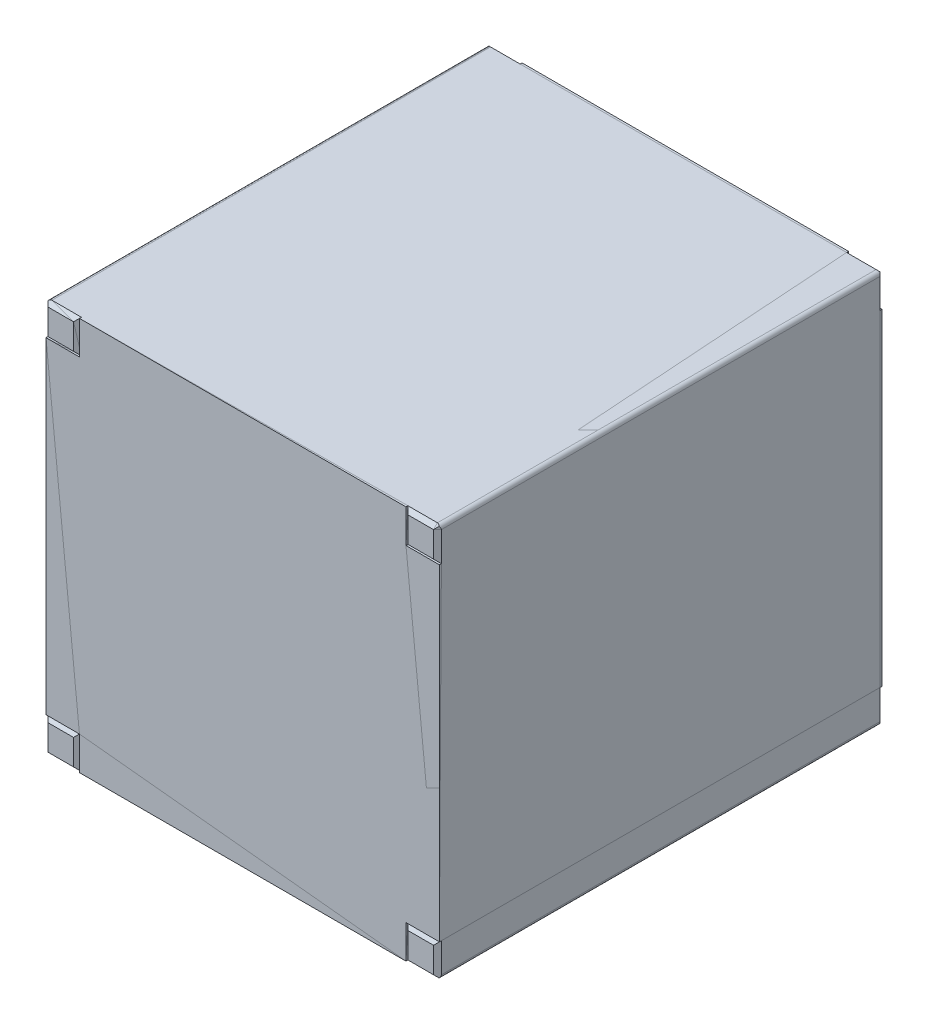
SolidWorks part; units mm, degrees
ref_plane "Front Plane" through (0, 0, 0) normal (0, 0, 1) x (1, 0, 0)
ref_plane "Top Plane" through (0, 0, 0) normal (0, 1, 0) x (1, 0, 0)
ref_plane "Right Plane" through (0, 0, 0) normal (1, 0, 0) x (0, 0, -1)
sketch "Sketch1" plane through (0, 0, 0) normal (0, 0, 1) x (1, 0, 0)
  line L1 (-50, -50) -> (50, -50) construction
  line L2 (-50, -50) -> (-50, 50) construction
  line L3 (-50, 50) -> (50, 50) construction
  line L4 (50, -50) -> (50, 50) construction
  line L5 (-50, -50) -> (50, 50) construction
  line L6 (-50, 50) -> (50, -50) construction
  line L23 (-50, 50) -> (-41.5, 50)
  line L24 (-50, 50) -> (-50, 41.5)
  line L25 (-50, 41.5) -> (-41.5, 41.5)
  line L26 (-41.5, 50) -> (-41.5, 41.5)
  line L27 (50, 50) -> (41.5, 50)
  line L28 (50, 50) -> (50, 41.5)
  line L29 (50, 41.5) -> (41.5, 41.5)
  line L30 (41.5, 50) -> (41.5, 41.5)
  line L31 (50, -50) -> (41.5, -50)
  line L32 (50, -50) -> (50, -41.5)
  line L33 (50, -41.5) -> (41.5, -41.5)
  line L34 (41.5, -50) -> (41.5, -41.5)
  line L35 (-50, -50) -> (-41.5, -50)
  line L36 (-50, -50) -> (-50, -41.5)
  line L37 (-50, -41.5) -> (-41.5, -41.5)
  line L38 (-41.5, -50) -> (-41.5, -41.5)
  point P0 (0, 0)
  dimension "D1" = 100
  dimension "D2" = 100
  dimension "D3" = 8.5
extrude "Boss-Extrude1" add sketch "Sketch1" along normal blind 56.75 and the other way blind 56.75
sketch "Sketch2" plane through (0, 0, 0) normal (0, 0, 1) x (1, 0, 0)
  line L1 (-50, -50) -> (50, -50)
  line L2 (-50, -50) -> (-50, 50)
  line L3 (-50, 50) -> (50, 50)
  line L4 (50, -50) -> (50, 50)
  line L5 (-50, -50) -> (50, 50) construction
  line L6 (-50, 50) -> (50, -50) construction
  point P0 (0, 0)
extrude "Boss-Extrude2" add sketch "Sketch2" along normal blind 50.25 and the other way blind 50.25
chamfer "Chamfer2" distance 1 angle 45 32 edges at (-45.75, -41.5, 56.75) (-41.5, -45.75, 56.75) (-45.75, -50, 56.75) (-50, -45.75, 56.75) (41.5, -45.75, 56.75) (45.75, -41.5, 56.75) (50, -45.75, 56.75) (45.75, -50, 56.75) (45.75, 41.5, 56.75) (41.5, 45.75, 56.75) (45.75, 50, 56.75) (50, 45.75, 56.75) (-41.5, 45.75, 56.75) (-45.75, 41.5, 56.75) (-50, 45.75, 56.75) (-45.75, 50, 56.75) (41.5, 45.75, -56.75) (45.75, 41.5, -56.75) (50, 45.75, -56.75) (45.75, 50, -56.75) (-45.75, 41.5, -56.75) (-41.5, 45.75, -56.75) (-45.75, 50, -56.75) (-50, 45.75, -56.75) (-41.5, -45.75, -56.75) (-45.75, -41.5, -56.75) (-50, -45.75, -56.75) (-45.75, -50, -56.75) (45.75, -41.5, -56.75) (41.5, -45.75, -56.75) (45.75, -50, -56.75) (50, -45.75, -56.75)
fillet "Fillet1" radius 1 4 edges at (50, -50, 0) (-50, -50, 0) (-50, 50, 0) (50, 50, 0)
sketch "Sketch3" plane through (0, 0, 50.25) normal (0, 0, 1) x (1, 0, 0)
  line L0 (-41.5, 50) -> (41.5, 50)
  line L1 (41.5, 50) -> (41.5, 41.5)
  line L2 (41.5, 41.5) -> (50, 41.5)
  line L3 (50, 41.5) -> (50, -41.5)
  line L4 (50, -41.5) -> (41.5, -41.5)
  line L5 (41.5, -41.5) -> (41.5, -50)
  line L6 (41.5, -50) -> (-41.5, -50)
  line L8 (-50, -41.5) -> (-50, 41.5)
  line L9 (-50, 41.5) -> (-41.5, 41.5)
  line L10 (-41.5, 41.5) -> (-41.5, 50)
  line L11 (-50, -41.5) -> (-41.5, -41.5)
  line L12 (-41.5, -41.5) -> (-41.5, -50)
extrude "Boss-Extrude3" add sketch "Sketch3" along normal blind 6
mirror "Mirror1" about plane through (0, 0, 0) normal (0, 0, 1) of "Boss-Extrude3"
surface "Surface-Offset1" parameters "D1"=0
equation "\"D1@Boss-Extrude1\"=113.5/2mm"
equation "\"D2@Boss-Extrude1\"=113.5/2"
